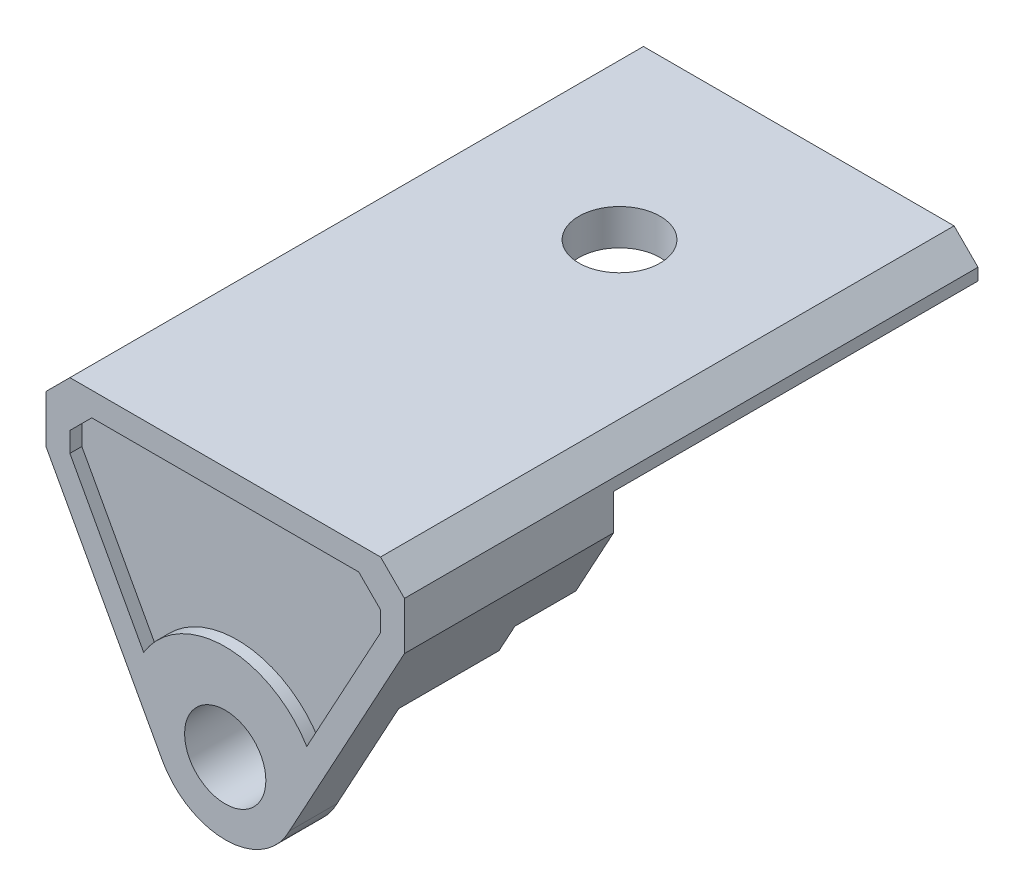
SolidWorks part; units mm, degrees
ref_plane "Front Plane" through (0, 0, 0) normal (0, 0, 1) x (1, 0, 0)
ref_plane "Top Plane" through (0, 0, 0) normal (0, 1, 0) x (1, 0, 0)
ref_plane "Right Plane" through (0, 0, 0) normal (1, 0, 0) x (0, 0, -1)
sketch "Sketch1" plane through (0, 0, 0) normal (0, 0, 1) x (1, 0, 0)
  line L0 (4.5962, 4.5962) -> (5.3033, 5.3033) construction
  line L1 (-4.5962, 4.5962) -> (-5.3033, 5.3033) construction
  line L2 (4.5962, 4.5962) -> (5.3033, 5.3033)
  line L3 (-4.5962, 4.5962) -> (-5.3033, 5.3033)
  line L4 (4.5941, 4.8769) -> (5.1619, 5.4447)
  line L5 (-4.5941, 4.8769) -> (-5.1619, 5.4447)
  line L6 (-4.5962, 4.5962) -> (-4.4548, 4.4548)
  line L8 (4.5962, 4.5962) -> (4.4548, 4.4548)
  circle A2 centre (0, 0) radius 7.5
  arc A4 (4.5941, 4.8769) -> (-4.5941, 4.8769) centre (0, 0) ccw
  circle A5 centre (0, 0) radius 6.3
  arc A7 (4.5962, 4.5962) -> (-4.5962, 4.5962) centre (0, 0) ccw construction
  dimension "D1" = 0.2
  dimension "D2" = 12.6
extrude "Boss-Extrude1" add sketch "Sketch1" against normal up to surface (2 mm away) contours A4 L4 A2 L5 region at (4.8017, 5.2352, 0)
extrude "Boss-Extrude2" add sketch "Sketch1<3>" along normal blind 4.75 contours A4 L4 A2 L5 region at (4.8017, 5.2352, 0)
sketch "Sketch1<3>" plane through (0, 0, 0) normal (0, 0, 1) x (1, 0, 0) same geometry as "Sketch1"
sketch "Sketch3" plane through (0, 0, 4.75) normal (0, 0, 1) x (1, 0, 0)
  line L0 (-5.16, 5.4428) -> (-2.821, -1.0208)
  line L1 (5.16, 5.4428) -> (2.821, -1.0208)
  line L2 (2.7807, 4.7453) -> (1.9028, 2.3194)
  line L3 (-2.7807, 4.7453) -> (-1.9028, 2.3194)
  line L4 (-2.7807, 4.7453) -> (-0.9403, -0.3403) construction
  line L5 (2.7807, 4.7453) -> (0.9403, -0.3403) construction
  circle A0 centre (0, 0) radius 3
  circle A1 centre (0, 0) radius 1.7 construction
  arc A2 (5.16, 5.4428) -> (-5.16, 5.4428) centre (0, 0) ccw construction
  arc A3 (5.16, 5.4428) -> (-5.16, 5.4428) centre (0, 0) ccw
  arc A4 (2.7807, 4.7453) -> (-2.7807, 4.7453) centre (0, 0) ccw
  circle A6 centre (0, 0) radius 1.7
  arc M3 (-4.5941, 4.8769) -> (4.5941, 4.8769) centre (0, 0) cw
  line M4 (4.5941, 4.8769) -> (5.16, 5.4428)
  arc M5 (5.16, 5.4428) -> (-5.16, 5.4428) centre (0, 0) ccw
  line M6 (-5.16, 5.4428) -> (-4.5941, 4.8769)
  dimension "D1" = 6
  dimension "D2" = 2
extrude "Boss-Extrude3" add sketch "Sketch3" along normal blind 2 contours A4 L2 A0 L1 L0 L3 M4 M3 M6 | M6 M3 M4 M5 | A0 A6 | L2 A4 L3 A0 region at (-4.9682, 5.0687, 4.75) region at (0, 7.3935, 4.75) region at (-2.8109, 0.7727, 4.75) region at (0, 4.0816, 4.75)
sketch "Sketch4" plane through (0, 0, 4.75) normal (0, 0, -1) x (-1, 0, 0)
  circle A2 centre (0, 0) radius 2.2
  circle A3 centre (0, 0) radius 2.2
  circle M6 centre (0, 0) radius 1.7
  dimension "D1" = 0.5
extrude "Boss-Extrude4" add sketch "Sketch4" along normal blind 0.5 contours A3 M6 region at (2.1378, 0, 4.75)
chamfer "Chamfer1" distance 0.5 angle 45 1 edges at (2.2, 0, 4.75)
sketch "Sketch5" plane through (0, 0, 6.75) normal (0, 0, 1) x (1, 0, 0)
  line L0 (0, 10.5) -> (0, 7.5) construction
  line L1 (-7.5, 10.5) -> (7.5, 10.5)
  line L2 (-7.5, 10.5) -> (-7.5, 7.5)
  line L3 (-7.5, 7.5) -> (7.5, 7.5)
  line L4 (7.5, 10.5) -> (7.5, 7.5)
  line L5 (-7.5, 7.5) -> (-2.6347, -1.4347)
  line L6 (7.5, 7.5) -> (2.5835, -1.525)
  arc A0 (-2.821, -1.0208) -> (2.821, -1.0208) centre (0, 0) ccw construction
  arc A1 (5.16, 5.4428) -> (-5.16, 5.4428) centre (0, 0) ccw construction
  arc A2 (-2.821, -1.0208) -> (2.821, -1.0208) centre (0, 0) ccw
  line M12 (2.821, -1.0208) -> (5.16, 5.4428)
  arc M13 (5.16, 5.4428) -> (-5.16, 5.4428) centre (0, 0) ccw
  line M14 (-5.16, 5.4428) -> (-2.821, -1.0208)
  arc M15 (-2.821, -1.0208) -> (2.821, -1.0208) centre (0, 0) ccw
  dimension "D1" = 15
  dimension "D2" = 3
extrude "Boss-Extrude5" add sketch "Sketch5" against normal up to surface (2 mm away) contours L3 L5 M15 M14 M13 | L0 L1 L2 L3 | L1 L0 L3 L4 | L6 L3 M13 M12 M15 region at (3.75, 9, 6.75) region at (-3.75, 9, 6.75) region at (-2.8207, 7.0751, 6.75) region at (3.75, 7.384, 6.75) up to face at (2.7, 0, 4.75)
sketch "Sketch6" plane through (0, 0, 4.75) normal (0, 0, -1) x (-1, 0, 0)
  line L0 (-2.6823, -1.3436) -> (-7.5, 7.5)
  line L1 (2.6347, -1.4347) -> (7.5, 7.5)
  line L2 (-4.5941, 4.8769) -> (-5.16, 5.4428)
  line L3 (4.5941, 4.8769) -> (5.16, 5.4428)
  line L4 (-4.5941, 4.8769) -> (-4.2855, 4.5494)
  line L5 (-5.4992, 3.8273) -> (-5.2563, 3.3814)
  line L6 (4.5941, 4.8769) -> (4.2757, 4.5586)
  arc A0 (5.4997, 3.8266) -> (-5.4992, 3.8273) centre (0, 0) ccw
  arc A1 (5.922, 4.6022) -> (-5.9216, 4.6027) centre (0, 0) ccw
  circle A2 centre (0, 0) radius 6.25
  line M9 (-4.5941, 4.8769) -> (-5.16, 5.4428)
  line M11 (5.16, 5.4428) -> (4.5941, 4.8769)
  dimension "D1" = 12.5
extrude "Boss-Extrude6" add sketch "Sketch6" along normal blind 4.2 contours A1 L0 A0 M9 | L1 A1 A0 M11 | A2 L4 A0 L0 | A2 L1 A0 L6 region at (4.9277, 4.1738, 4.75) region at (5.3001, 4.6896, 4.75) region at (-4.9255, 4.1757, 4.75) region at (-5.3003, 4.6893, 4.75)
sketch "Sketch8" plane through (0, 0, 4.75) normal (0, 0, -1) x (-1, 0, 0)
  line L5 (5.922, 4.6022) -> (7.5, 7.5)
  line L6 (7.5, 7.5) -> (7.5, 10.5)
  line L7 (7.5, 10.5) -> (-7.5, 10.5)
  line L8 (-7.5, 10.5) -> (-7.5, 7.5)
  line L9 (-7.5, 7.5) -> (-5.9216, 4.6027)
  line L10 (5.922, 4.6022) -> (7.5, 7.5)
  line L11 (7.5, 7.5) -> (7.5, 10.5)
  line L12 (7.5, 10.5) -> (-7.5, 10.5)
  line L13 (-7.5, 10.5) -> (-7.5, 7.5)
  line L14 (-7.5, 7.5) -> (-5.9216, 4.6027)
  arc A1 (5.922, 4.6022) -> (-5.9216, 4.6027) centre (0, 0) ccw
  arc A2 (5.922, 4.6022) -> (-5.9216, 4.6027) centre (0, 0) ccw
  dimension "D1" = 0
extrude "Boss-Extrude8" add sketch "Sketch8" along normal up to surface (6.75 mm away) up to face at (0, 6.1299, -2)
sketch "Sketch10" plane through (0, 0, -2) normal (0, 0, -1) x (-1, 0, 0)
  line L1 (-7.5, 10.5) -> (7.5, 10.5)
  line L2 (-7.5, 10.5) -> (-7.5, 7.5)
  line L3 (-7.5, 7.5) -> (7.5, 7.5)
  line L4 (7.5, 10.5) -> (7.5, 7.5)
extrude "Boss-Extrude9" add sketch "Sketch10" along normal blind 15.25
sketch "Sketch11" plane through (0, 7.5, 0) normal (0, -1, 0) x (1, 0, 0)
  line L3 (0, -17.25) -> (0, -9.5) construction
  line L4 (7.5, -17.25) -> (-7.5, -17.25) construction
  circle A0 centre (0, -9.5) radius 1.65
  dimension "D1" = 3.3
  dimension "D2" = 7.5
extrude "Cut-Extrude1" cut sketch "Sketch11" against normal through all
fillet "Fillet1" radius 0.2 2 edges at (-4.2757, 4.5586, 2.65) (4.2855, 4.5494, 2.65)
chamfer "Chamfer6" distance 1.5 angle 45 2 edges at (-7.5, 10.5, -5.25) (7.5, 10.5, -5.25)
sketch "Sketch13" plane through (0, 0, 6.75) normal (0, 0, 1) x (1, 0, 0)
  line L0 (-6.5, 7.7546) -> (-3.4131, 2.0858)
  line L1 (-6.5, 8.5858) -> (-6.5, 7.7546)
  line L2 (-5.5858, 9.5) -> (-6.5, 8.5858)
  line L3 (5.5858, 9.5) -> (-5.5858, 9.5)
  line L4 (6.5, 8.5858) -> (5.5858, 9.5)
  line L5 (6.5, 7.7547) -> (6.5, 8.5858)
  line L6 (3.4124, 2.087) -> (6.5, 7.7547)
  line L7 (6, 10.5) -> (-6, 10.5)
  line L8 (-6, 10.5) -> (-7.5, 9)
  line L9 (-7.5, 9) -> (-7.5, 7.5)
  line L10 (-7.5, 7.5) -> (-2.6347, -1.4347)
  line L11 (2.6823, -1.3436) -> (7.5, 7.5)
  line L12 (7.5, 7.5) -> (7.5, 9)
  line L13 (7.5, 9) -> (6, 10.5)
  line L14 (6, 10.5) -> (-6, 10.5)
  line L15 (-6, 10.5) -> (-7.5, 9)
  line L16 (-7.5, 9) -> (-7.5, 7.5)
  line L17 (-7.5, 7.5) -> (-2.6347, -1.4347)
  line L18 (2.6823, -1.3436) -> (7.5, 7.5)
  line L19 (7.5, 7.5) -> (7.5, 9)
  line L20 (7.5, 9) -> (6, 10.5)
  arc A1 (2.6823, -1.3436) -> (-2.6347, -1.4347) centre (0, 0) ccw
  arc A2 (3.4124, 2.087) -> (-3.4131, 2.0858) centre (0, 0) ccw
  arc A3 (-2.6347, -1.4347) -> (2.6823, -1.3436) centre (0, 0) ccw
  dimension "D1" = 0
  dimension "D2" = 1
sketch "Sketch16" plane through (0, 0, -17.25) normal (0, 0, -1) x (-1, 0, 0)
  line L0 (-7.5, 9) -> (-7.5, 10.5)
  line L1 (7.5, 9) -> (-7.5, 9)
  line L2 (7.5, 9) -> (7.5, 10.5)
  line L3 (7.5, 10.5) -> (-7.5, 10.5)
extrude "Boss-Extrude12" add sketch "Sketch16" against normal up to surface (24 mm away) up to face at (0.0094, 6.2014, 6.75)
extrude "Cut-Extrude3" cut sketch "Sketch13" against normal blind 0.5 contours A2 L6 L5 L4 L3 L2 L1 L0 region at (-0.0003, 6.6063, 6.75)
sketch "Sketch17" plane through (0, 0, -17.25) normal (0, 0, -1) x (-1, 0, 0)
  line L0 (7.5, 10.5) -> (-7.5, 10.5) construction
  line L1 (-6.8841, 10.5) -> (7.5, 10.5)
  line L2 (-6.8841, 10.5) -> (-6.8841, 9)
  line L3 (-6.8841, 9) -> (7.5, 9)
  line L4 (7.5, 10.5) -> (7.5, 9)
  line L5 (7.5, 7.5) -> (7.5, 10.5) construction
  line L7 (-7.5, 7.5) -> (7.5, 7.5)
  line L8 (-7.5, 7.5) -> (-7.5, 9)
  line L9 (-7.5, 9) -> (7.5, 9)
  line L10 (7.5, 7.5) -> (7.5, 9)
  line M1 (7.5, 7.5) -> (7.5, 10.5)
  line M3 (-7.5, 10.5) -> (-7.5, 7.5)
  line M4 (-7.5, 7.5) -> (7.5, 7.5)
chamfer "Chamfer7" distance 1 angle 45 2 edges at (7.5, 10.5, -5.25) (-7.5, 10.5, -5.25)
extrude "Cut-Extrude4" cut sketch "Sketch17" against normal up to surface (15.25 mm away) contours L9 L3 M3 M4 M1 region at (0, 8.25, -17.25) up to face at (-0.0001, 5.837, -2)
sketch "Sketch18" plane through (0, 10.5, 0) normal (0, 1, 0) x (1, 0, 0)
  line L0 (-6.5, 17.25) -> (6.5, 17.25) construction
  circle A0 centre (0, 9.75) radius 1.7
  dimension "D1" = 3.4
  dimension "D2" = 7.5
extrude "Cut-Extrude5" cut sketch "Sketch18" against normal blind 10
